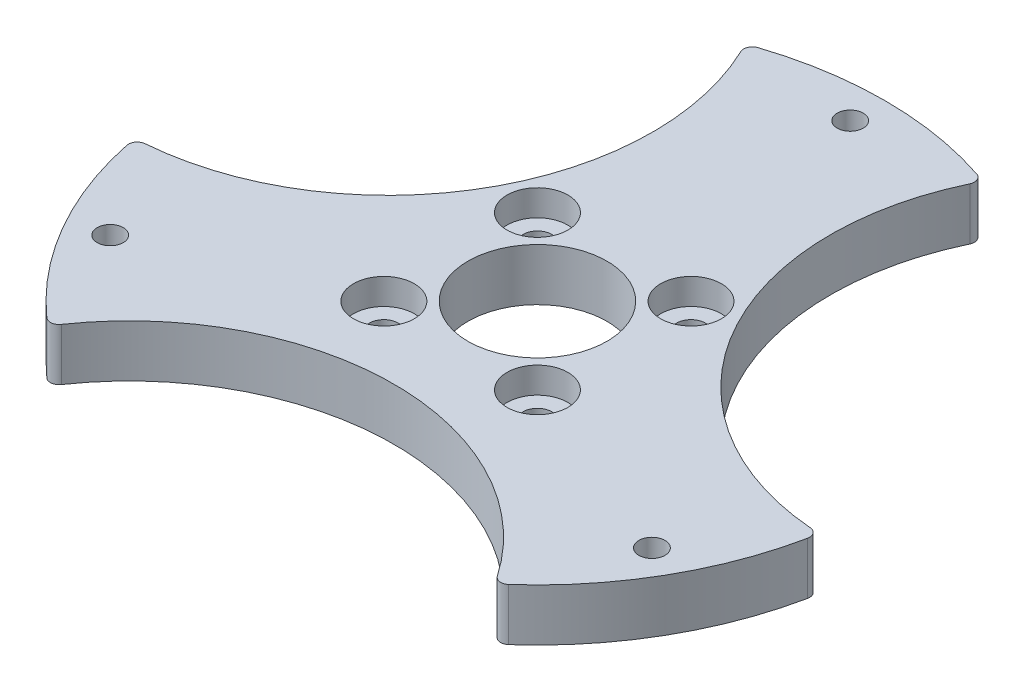
SolidWorks part; units mm, degrees
ref_plane "Front Plane" through (0, 0, 0) normal (0, 0, 1) x (1, 0, 0)
ref_plane "Top Plane" through (0, 0, 0) normal (0, 1, 0) x (1, 0, 0)
ref_plane "Right Plane" through (0, 0, 0) normal (1, 0, 0) x (0, 0, -1)
sketch "Sketch1" plane through (0, 0, 0) normal (0, 1, 0) x (1, 0, 0)
  circle A0 centre (0, 0) radius 40
  dimension "D1" = 80
extrude "Boss-Extrude1" add sketch "Sketch1" along normal blind 6
sketch "Sketch2" plane through (0, 0, 0) normal (0, 1, 0) x (1, 0, 0)
  line L0 (-13.6808, 37.5877) -> (0, 0) construction
  line L1 (0, 0) -> (13.6808, 37.5877) construction
  line L2 (0, -1000) -> (0, 49000) construction
  line L3 (-13.6808, 37.5877) -> (-10.9446, 30.0702)
  line L4 (13.6808, 37.5877) -> (10.9446, 30.0702)
  line L5 (39.3923, -6.9459) -> (31.5138, -5.5567)
  line L6 (25.7115, -30.6418) -> (20.5692, -24.5134)
  line L7 (-25.7115, -30.6418) -> (-20.5692, -24.5134)
  line L8 (-39.3923, -6.9459) -> (-31.5138, -5.5567)
  circle A0 centre (0, 0) radius 40 construction
  arc A1 (-13.6808, 37.5877) -> (13.6808, 37.5877) centre (0, 0) cw
  arc A2 (-10.9446, 30.0702) -> (10.9446, 30.0702) centre (0, 0) cw
  arc A3 (39.3923, -6.9459) -> (25.7115, -30.6418) centre (0, 0) cw
  arc A4 (31.5138, -5.5567) -> (20.5692, -24.5134) centre (0, 0) cw
  arc A5 (-25.7115, -30.6418) -> (-39.3923, -6.9459) centre (0, 0) cw
  arc A6 (-20.5692, -24.5134) -> (-31.5138, -5.5567) centre (0, 0) cw
  point P21 (0, 0)
  dimension "D1" = 20
  dimension "D2" = 20
  dimension "D3" = 8
  dimension "D4" = 3
sketch "Sketch3" plane through (0, 6, 0) normal (0, 1, 0) x (1, 0, 0)
  circle A0 centre (40.6986, 23.4973) radius 30.4713
extrude "Cut-Extrude1" cut sketch "Sketch3" against normal through all
sketch "Sketch5" plane through (0, 6, 0) normal (0, 1, 0) x (1, 0, 0)
  circle A0 centre (0, 36) radius 1.5
  point P2 (0, 0)
  point P4 (0, 0)
  dimension "D2" = 3
  dimension "D1" = 36
extrude "Cut-Extrude2" cut sketch "Sketch5" against normal through all
pattern_circular "CirPattern1" count 3 over 360 about axis through (0, 6, 0) along (0, -1, 0) of "Cut-Extrude1", "Cut-Extrude2" reverse direction yes
sketch "Sketch6" plane through (0, 6, 0) normal (0, 1, 0) x (1, 0, 0)
  line L1 (-8.8388, -8.8388) -> (8.8388, -8.8388) construction
  line L2 (-8.8388, -8.8388) -> (-8.8388, 8.8388) construction
  line L3 (-8.8388, 8.8388) -> (8.8388, 8.8388) construction
  line L4 (8.8388, -8.8388) -> (8.8388, 8.8388) construction
  line L5 (-8.8388, -8.8388) -> (8.8388, 8.8388) construction
  line L6 (-8.8388, 8.8388) -> (8.8388, -8.8388) construction
  circle A0 centre (8.8388, 8.8388) radius 1.65
  circle A1 centre (-8.8388, 8.8388) radius 1.65
  circle A2 centre (-8.8388, -8.8388) radius 1.65
  circle A3 centre (8.8388, -8.8388) radius 1.65
  point P0 (0, 0)
  dimension "D1" = 3.3
  dimension "D2" = 12.5
extrude "Cut-Extrude3" cut sketch "Sketch6" against normal through all
sketch "Sketch7" plane through (0, 6, 0) normal (0, 1, 0) x (1, 0, 0)
  circle A0 centre (0, 0) radius 8
  dimension "D1" = 16
extrude "Cut-Extrude4" cut sketch "Sketch7" against normal through all
fillet "Fillet1" radius 1 6 edges at (-39.3923, 3, 6.9459) (-13.6808, 3, -37.5877) (25.7115, 3, 30.6418) (-25.7115, 3, 30.6418) (39.3923, 3, 6.9459) (13.6808, 3, -37.5877)
sketch "Sketch8" plane through (0, 6, 0) normal (0, -1, 0) x (1, 0, 0)
  circle A0 centre (8.8388, 8.8388) radius 3.5
  circle A1 centre (8.8388, -8.8388) radius 3.5
  circle A2 centre (-8.8388, 8.8388) radius 3.5
  circle A3 centre (-8.8388, -8.8388) radius 3.5
  dimension "D1" = 7
extrude "Cut-Extrude5" cut sketch "Sketch8" along normal blind 3
